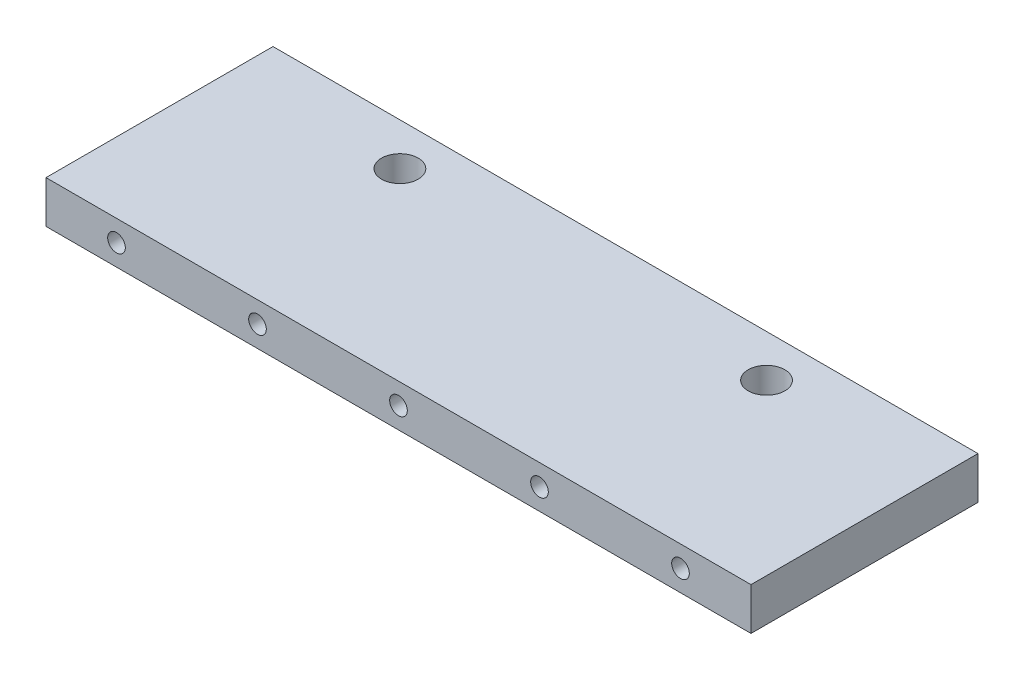
SolidWorks part; units mm, degrees
material "6061-T6 (SS)"
ref_plane "Front Plane" through (0, 0, 0) normal (0, 0, 1) x (1, 0, 0)
ref_plane "Top Plane" through (0, 0, 0) normal (0, 1, 0) x (1, 0, 0)
ref_plane "Right Plane" through (0, 0, 0) normal (1, 0, 0) x (0, 0, -1)
sketch "Sketch1" plane through (0, 0, 0) normal (0, 1, 0) x (1, 0, 0)
  line L1 (0, 0) -> (100, 0)
  line L2 (0, 0) -> (0, 32.2)
  line L3 (0, 32.2) -> (100, 32.2)
  line L4 (100, 0) -> (100, 32.2)
  dimension "D1" = 100
  dimension "D2" = 32.2
extrude "Boss-Extrude1" add sketch "Sketch1" along normal blind 6
sketch "Sketch5" plane through (0, 0, -32.2) normal (0, 0, -1) x (-1, 0, 0)
  line L1 (-100, 0) -> (0, 0) construction
  line L3 (-50, 3) -> (-50, 6) construction
  line L4 (-100, 6) -> (0, 6) construction
  point P0 (-90, 3)
  point P12 (-70, 3)
  point P13 (-50, 3)
  point P14 (-30, 3)
  point P15 (-10, 3)
  dimension "D1" = 3
  dimension "D2" = 5
  dimension "D3" = 20
hole_wizard "Tap Drill for M3 Tap1" positions "Sketch5" profile "Sketch7" hole size "M3" standard "DIN" end condition through all
sketch "Sketch7" plane through (90, 3, -32.2) normal (1, 0, 0) x (0, 1, 0)
  line L0 (0, 0) -> (0, 32.2)
  line L1 (0, 32.2) -> (1.25, 32.2)
  line L2 (1.25, 32.2) -> (1.25, 0)
  line L5 (1.25, 0) -> (0, 0)
  line L11 (0, -6.35) -> (0, 107.95) construction
  dimension "Thru Hole Dia." = 2.5
  dimension "Thru Hole Depth" = 32.2
sketch "Sketch10" plane through (0, 6, 0) normal (0, 1, 0) x (1, 0, 0)
  line L0 (0, 26.2) -> (100, 26.2) construction
  line L1 (0, 32.2) -> (0, 0) construction
  line L2 (100, 0) -> (100, 32.2) construction
  line L3 (76, 26.2) -> (24, 26.2)
  point P0 (24, 26.2)
  point P3 (76, 26.2)
  point P29 (50, 26.2)
  dimension "D1" = 52
  dimension "D2" = 6
hole_wizard "Tap Drill for M5 Helicoil1" positions "Sketch10" profile "Sketch11" hole size "M5x0.8" standard "DIN" end condition through all
sketch "Sketch11" plane through (24, 6, -26.2) normal (1, 0, 0) x (0, 0, 1)
  line L0 (0, 0) -> (0, 6)
  line L1 (0, 6) -> (2.6, 6)
  line L2 (2.6, 6) -> (2.6, 0)
  line L5 (2.6, 0) -> (0, 0)
  line L11 (0, -6.35) -> (0, 107.95) construction
  dimension "Thru Hole Dia." = 5.2
  dimension "Thru Hole Depth" = 6
